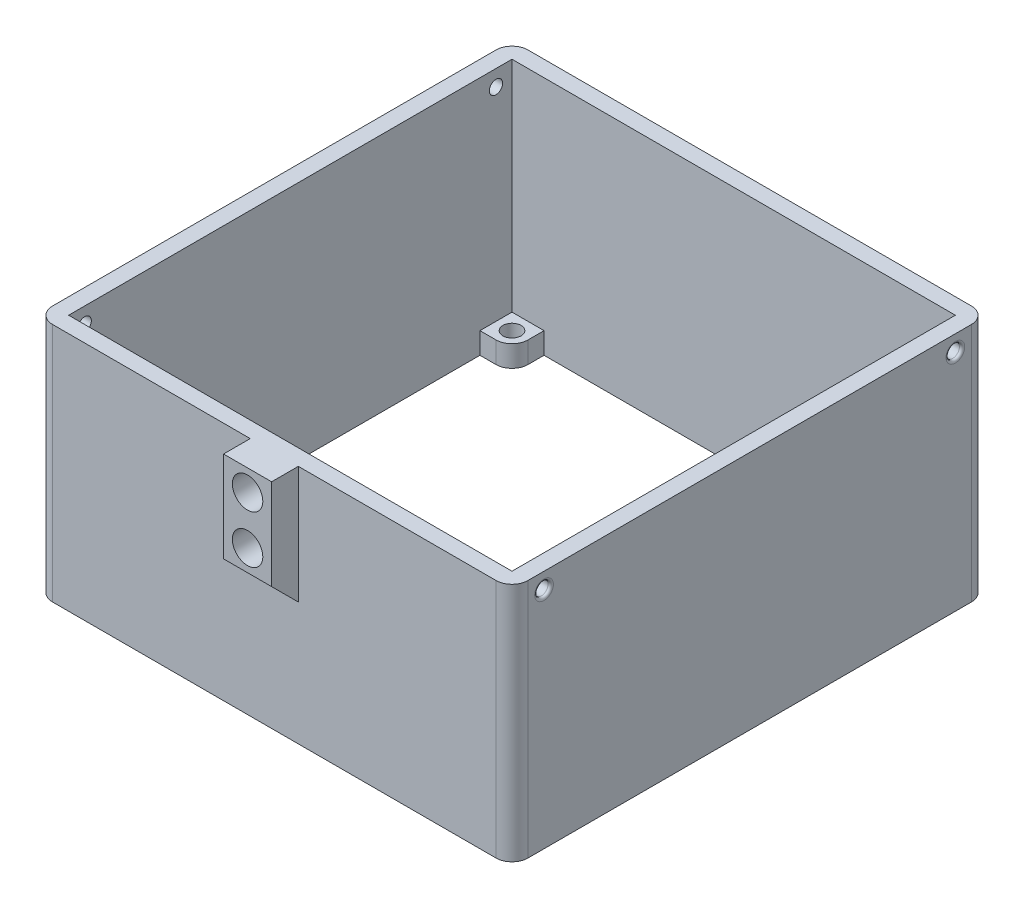
SolidWorks part; units mm, degrees
ref_plane "Front Plane" through (0, 0, 0) normal (0, 0, 1) x (1, 0, 0)
ref_plane "Top Plane" through (0, 0, 0) normal (0, 1, 0) x (1, 0, 0)
ref_plane "Right Plane" through (0, 0, 0) normal (1, 0, 0) x (0, 0, -1)
sketch "Sketch1" plane through (0, 0, 0) normal (0, 1, 0) x (1, 0, 0)
  line L0 (44.5, 89) -> (44.5, 0) construction
  line L1 (0, 0) -> (89, 0)
  line L2 (0, 0) -> (0, 89)
  line L3 (0, 89) -> (89, 89)
  line L4 (89, 0) -> (89, 89)
  line L5 (3, 3) -> (86, 3)
  line L6 (3, 3) -> (3, 86)
  line L7 (3, 86) -> (86, 86)
  line L8 (86, 3) -> (86, 86)
  dimension "D1" = 3
  dimension "D2" = 3
  dimension "D3" = 83
  dimension "D4" = 3
extrude "Boss-Extrude1" add sketch "Sketch1" along normal mid plane 45
sketch "Sketch4" plane through (0, -22.5, 0) normal (0, -1, 0) x (1, 0, 0)
  line L0 (80, -3) -> (86, -3)
  line L1 (3, -3) -> (9, -3)
  line L2 (3, -3) -> (3, -9)
  line L3 (3, -9) -> (9, -9)
  line L4 (9, -3) -> (9, -9)
  line L17 (80, -3) -> (80, -9)
  line L18 (80, -9) -> (86, -9)
  line L19 (86, -3) -> (86, -9)
  line L21 (80, -80) -> (86, -80)
  line L22 (80, -80) -> (80, -86)
  line L23 (80, -86) -> (86, -86)
  line L24 (86, -80) -> (86, -86)
  line L29 (3, -80) -> (9, -80)
  line L30 (3, -80) -> (3, -86)
  line L31 (3, -86) -> (9, -86)
  line L32 (9, -80) -> (9, -86)
  circle A0 centre (6, -6) radius 1.7
  circle A1 centre (83, -6) radius 1.7
  circle A2 centre (83, -83) radius 1.7
  circle A4 centre (6, -83) radius 1.7
  point P7 (6, -3)
  point P8 (9, -6)
  point P17 (83, -3)
  point P18 (86, -6)
  point P30 (83, -80)
  point P31 (86, -83)
  point P38 (6, -80)
  point P39 (9, -83)
  dimension "D1" = 3.4
  dimension "D4" = 3.4
  dimension "D7" = 3.4
  dimension "D10" = 3.4
  dimension "D2" = 6
  dimension "D3" = 6
  dimension "D5" = 6
  dimension "D6" = 6
  dimension "D8" = 6
  dimension "D9" = 6
  dimension "D11" = 6
  dimension "D12" = 6
extrude "Boss-Extrude3" add sketch "Sketch4" against normal blind 4
fillet "Fillet3" radius 3 4 edges at (9, -20.5, -80) (80, -20.5, -80) (9, -20.5, -9) (80, -20.5, -9)
sketch "Sketch6" plane through (0, 0, 0) normal (0, 0, 1) x (1, 0, 0)
  line L0 (0, 22.5) -> (89, 22.5) construction
  line L1 (40, 22.5) -> (49, 22.5)
  line L2 (40, 22.5) -> (40, 5.5)
  line L3 (40, 5.5) -> (49, 5.5)
  line L4 (49, 22.5) -> (49, 5.5)
  line L5 (44.5, -22.5) -> (44.5, 22.5) construction
  line L6 (0, -22.5) -> (89, -22.5) construction
  line L7 (40, 14) -> (49, 14) construction
  circle A0 centre (44.5, 18.5) radius 2.85
  circle A1 centre (44.5, 9.5) radius 2.85
  dimension "D3" = 5.7
  dimension "D1" = 17
  dimension "D2" = 9
  dimension "D4" = 9
extrude "Boss-Extrude4" add sketch "Sketch6" along normal blind 5
chamfer "Chamfer1" distance 5 angle 45 1 edges at (44.5, 5.5, 0)
fillet "Fillet4" radius 3 4 edges at (0, 0, 0) (89, 0, 0) (0, 0, -89) (89, 0, -89)
sketch "Sketch7" plane through (89, 0, 0) normal (1, 0, 0) x (0, 0, -1)
  line L0 (3, 22.5) -> (86, 22.5) construction
  line L1 (44.5, 22.5) -> (44.5, -22.5) construction
  line L2 (3, -22.5) -> (86, -22.5) construction
  line L3 (3, 22.5) -> (3, -22.5) construction
  circle A0 centre (83, 19.5) radius 1.25
  circle A1 centre (6, 19.5) radius 1.25
  point P4 (0, 0)
  dimension "D1" = 2.5
  dimension "D2" = 3
  dimension "D3" = 3
extrude "Cut-Extrude1" cut sketch "Sketch7" against normal through all
fillet "Fillet5" radius 0.5 4 edges at (0, 19.5, -7.25) (0, 19.5, -84.25) (89, 19.5, -84.25) (89, 19.5, -7.25)
